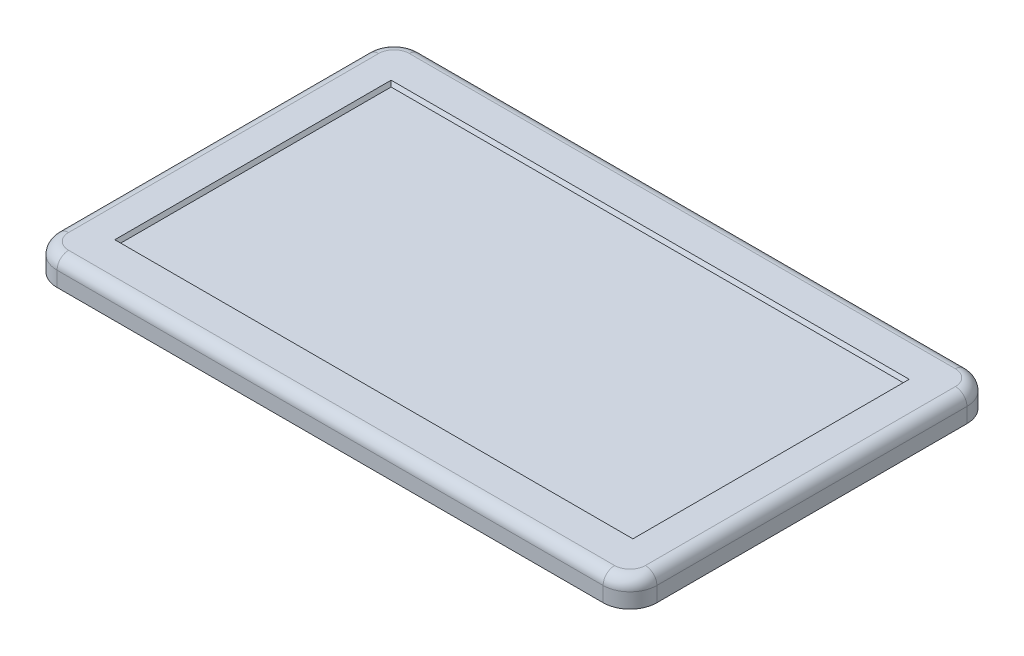
SolidWorks part; units mm, degrees
ref_plane "Front Plane" through (0, 0, 0) normal (0, 0, 1) x (1, 0, 0)
ref_plane "Top Plane" through (0, 0, 0) normal (0, 1, 0) x (1, 0, 0)
ref_plane "Right Plane" through (0, 0, 0) normal (1, 0, 0) x (0, 0, -1)
sketch "Sketch1" plane through (0, 0, 0) normal (0, 1, 0) x (1, 0, 0)
  line L1 (-150.5839, -100.33) -> (150.5839, -100.33)
  line L2 (-165.4175, -85.4964) -> (-165.4175, 85.4964)
  line L3 (-150.5839, 100.33) -> (150.5839, 100.33)
  line L4 (165.4175, -85.4964) -> (165.4175, 85.4964)
  line L5 (-165.4175, -100.33) -> (165.4175, 100.33) construction
  line L6 (-165.4175, 100.33) -> (165.4175, -100.33) construction
  arc A0 (150.5839, -100.33) -> (165.4175, -85.4964) centre (150.5839, -85.4964) ccw
  arc A1 (165.4175, 85.4964) -> (150.5839, 100.33) centre (150.5839, 85.4964) ccw
  arc A2 (-150.5839, 100.33) -> (-165.4175, 85.4964) centre (-150.5839, 85.4964) ccw
  arc A3 (-150.5839, -100.33) -> (-165.4175, -85.4964) centre (-150.5839, -85.4964) cw
  point P0 (0, 0)
  dimension "D3" = 14.8336
  dimension "D1" = 330.835
  dimension "D2" = 200.66
extrude "Boss-Extrude1" add sketch "Sketch1" along normal blind 14.605
fillet "Fillet1" radius 6.35 8 edges at (-161.0728, 14.605, 95.9853) (-165.4175, 14.605, 0) (-161.0728, 14.605, -95.9853) (0, 14.605, -100.33) (161.0728, 14.605, -95.9853) (165.4175, 14.605, 0) (161.0728, 14.605, 95.9853) (0, 14.605, 100.33)
sketch "Sketch2" plane through (0, 0, 0) normal (0, -1, 0) x (1, 0, 0)
  line L0 (165.4175, 85.4964) -> (165.4175, -85.4964) construction
  line L1 (-148.6789, -98.425) -> (148.6789, -98.425)
  line L2 (-163.5125, -83.5914) -> (-163.5125, 83.5914)
  line L3 (-148.6789, 98.425) -> (148.6789, 98.425)
  line L4 (163.5125, -83.5914) -> (163.5125, 83.5914)
  line L5 (-163.5125, -98.425) -> (163.5125, 98.425) construction
  line L6 (-163.5125, 98.425) -> (163.5125, -98.425) construction
  line L7 (-150.5839, 100.33) -> (150.5839, 100.33) construction
  arc A0 (148.6789, 98.425) -> (163.5125, 83.5914) centre (148.6789, 83.5914) cw
  arc A1 (163.5125, -83.5914) -> (148.6789, -98.425) centre (148.6789, -83.5914) cw
  arc A2 (-148.6789, -98.425) -> (-163.5125, -83.5914) centre (-148.6789, -83.5914) cw
  arc A3 (-163.5125, 83.5914) -> (-148.6789, 98.425) centre (-148.6789, 83.5914) cw
  point P0 (0, 0)
  dimension "D3" = 14.8336
  dimension "D1" = 1.905
  dimension "D2" = 1.905
extrude "Cut-Extrude1" cut sketch "Sketch2" against normal blind 12.7
sketch "Sketch3" plane through (0, 14.605, 0) normal (0, 1, 0) x (1, 0, 0)
  line L1 (-142.875, -76.2) -> (142.875, -76.2)
  line L2 (-142.875, -76.2) -> (-142.875, 76.2)
  line L3 (-142.875, 76.2) -> (142.875, 76.2)
  line L4 (142.875, -76.2) -> (142.875, 76.2)
  line L5 (-142.875, -76.2) -> (142.875, 76.2) construction
  line L6 (-142.875, 76.2) -> (142.875, -76.2) construction
  point P0 (0, 0)
  dimension "D1" = 285.75
  dimension "D2" = 152.4
ref_plane "Plane1" through (0, 10.16, 0) normal (0, 1, 0) x (1, 0, 0)
sketch "Sketch4" plane through (0, 10.16, 0) normal (0, 1, 0) x (1, 0, 0)
  line L1 (-139.7, -73.025) -> (139.7, -73.025)
  line L2 (-139.7, -73.025) -> (-139.7, 73.025)
  line L3 (-139.7, 73.025) -> (139.7, 73.025)
  line L4 (139.7, -73.025) -> (139.7, 73.025)
  line L5 (-139.7, -73.025) -> (139.7, 73.025) construction
  line L6 (-139.7, 73.025) -> (139.7, -73.025) construction
  point P0 (0, 0)
  dimension "D1" = 279.4
  dimension "D2" = 146.05
loft "Cut-Loft1" cut profiles "Sketch3", "Sketch4" connector at (-142.875, 14.605, 76.2) connector at (-139.7, 10.16, 73.025)
sketch "Sketch5" plane through (0, 12.7, 0) normal (0, -1, 0) x (1, 0, 0)
  line L1 (-145.3668, 78.849) -> (145.3668, 78.849)
  line L2 (-145.3668, 78.849) -> (-145.3668, -78.849)
  line L3 (-145.3668, -78.849) -> (145.3668, -78.849)
  line L4 (145.3668, 78.849) -> (145.3668, -78.849)
  line L5 (-145.3668, 78.849) -> (145.3668, -78.849) construction
  line L6 (-145.3668, -78.849) -> (145.3668, 78.849) construction
  point P0 (0, 0)
extrude "Boss-Extrude2" add sketch "Sketch5" along normal blind 1.905
fillet "Fillet2" radius 2.54 4 edges at (0, 10.795, -78.849) (-145.3668, 10.795, 0) (0, 10.795, 78.849) (145.3668, 10.795, 0)
sketch "Sketch6" plane through (0, 12.7, 0) normal (0, 1, 0) x (1, 0, 0)
  line L0 (80, 200) -> (400, 200) construction
